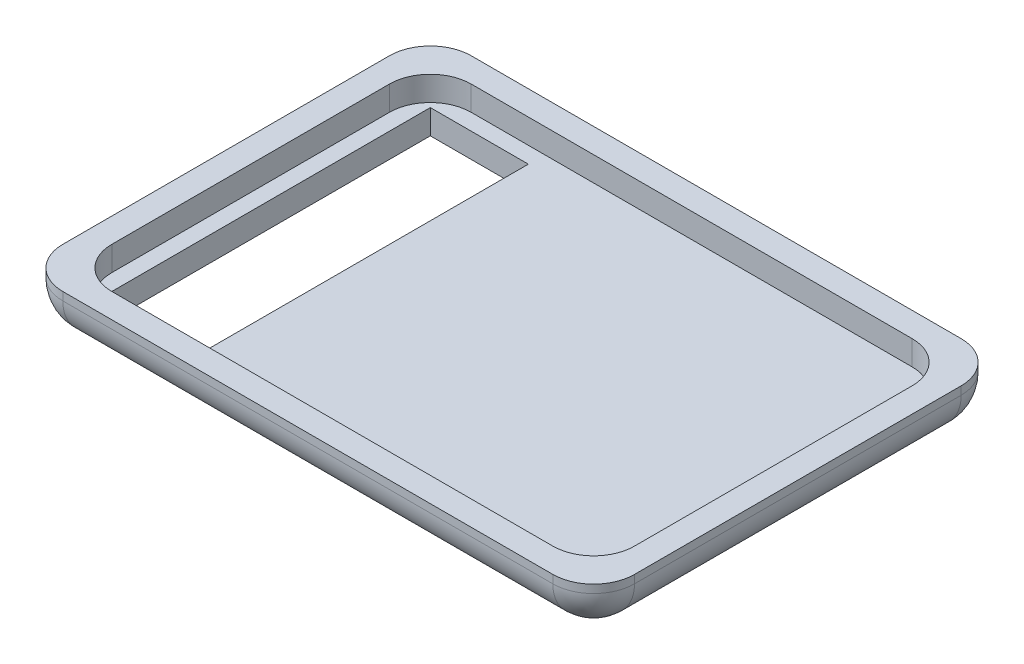
SolidWorks part; units mm, degrees
ref_plane "Front Plane" through (0, 0, 0) normal (0, 0, 1) x (1, 0, 0)
ref_plane "Top Plane" through (0, 0, 0) normal (0, 1, 0) x (1, 0, 0)
ref_plane "Right Plane" through (0, 0, 0) normal (1, 0, 0) x (0, 0, -1)
sketch "Sketch1" plane through (0, 0, 0) normal (0, 1, 0) x (1, 0, 0)
  line L1 (-35, 25) -> (35, 25)
  line L2 (-35, 25) -> (-35, -25)
  line L3 (-35, -25) -> (35, -25)
  line L4 (35, 25) -> (35, -25)
  line L5 (-35, 25) -> (35, -25) construction
  line L6 (-35, -25) -> (35, 25) construction
  point P0 (0, 0)
  dimension "D1" = 70
  dimension "D2" = 50
extrude "Boss-Extrude1" add sketch "Sketch1" along normal blind 6
shell "Shell1" thickness 3 removed face at (0, 6, 0)
fillet "Fillet1" radius 5 1 edges at (35, 3, 25) type face fillet first side face at (0, 3, 25) second side face at (35, 3, 0)
fillet "Fillet2" radius 5 1 edges at (35, 3, -25) type face fillet first side face at (35, 3, -2.5) second side face at (0, 3, -25)
fillet "Fillet3" radius 5 1 edges at (-35, 3, 25) type face fillet first side face at (-2.5, 3, 25) second side face at (-35, 3, 0)
fillet "Fillet4" radius 5 1 edges at (-35, 3, -25) type face fillet first side face at (-35, 3, -2.5) second side face at (-2.5, 3, -25)
fillet "Fillet5" radius 5 8 edges at (-33.5355, 0, -23.5355) (-33.5355, 0, 23.5355) (33.5355, 0, -23.5355) (33.5355, 0, 23.5355) (35, 0, 0) (0, 0, -25) (-35, 0, 0) (0, 0, 25) type face fillet first side face at (0, 0, 0) second side face at (33.0178, 3, -23.0178) second side face at (35, 3, 0) second side face at (33.0178, 3, 23.0178) second side face at (0, 3, 25) second side face at (-33.0178, 3, 23.0178) second side face at (-35, 3, 0) second side face at (-33.0178, 3, -23.0178) second side face at (0, 3, -25)
fillet "Fillet6" radius 5 1 edges at (32, 4.5, 22) type face fillet first side face at (0, 4.5, 22) second side face at (32, 4.5, 0)
fillet "Fillet7" radius 5 1 edges at (-32, 4.5, 22) type face fillet first side face at (-2.5, 4.5, 22) second side face at (-32, 4.5, 0)
fillet "Fillet8" radius 5 1 edges at (-32, 4.5, -22) type face fillet first side face at (-32, 4.5, -2.5) second side face at (0, 4.5, -22)
fillet "Fillet9" radius 5 1 edges at (32, 4.5, -22) type face fillet first side face at (2.5, 4.5, -22) second side face at (32, 4.5, -2.5)
sketch "Sketch2" plane through (0, 0, 0) normal (0, -1, 0) x (1, 0, 0)
  line L0 (30, 20) -> (-30, 20) construction
  line L1 (-30, 20) -> (-18, 20)
  line L2 (-30, 20) -> (-30, -20)
  line L3 (-30, -20) -> (-18, -20)
  line L4 (-18, 20) -> (-18, -20)
  line L5 (-30, 20) -> (-18, -20) construction
  line L6 (-30, -20) -> (-18, 20) construction
  line L7 (-30, -20) -> (30, -20) construction
  line L8 (-30, 20) -> (-30, -20) construction
  point P0 (-24, 0)
  dimension "D1" = 0
  dimension "D2" = 0
  dimension "D3" = 0
  dimension "D4" = 12
extrude "Cut-Extrude1" cut sketch "Sketch2" against normal blind 10 and the other way blind 10
